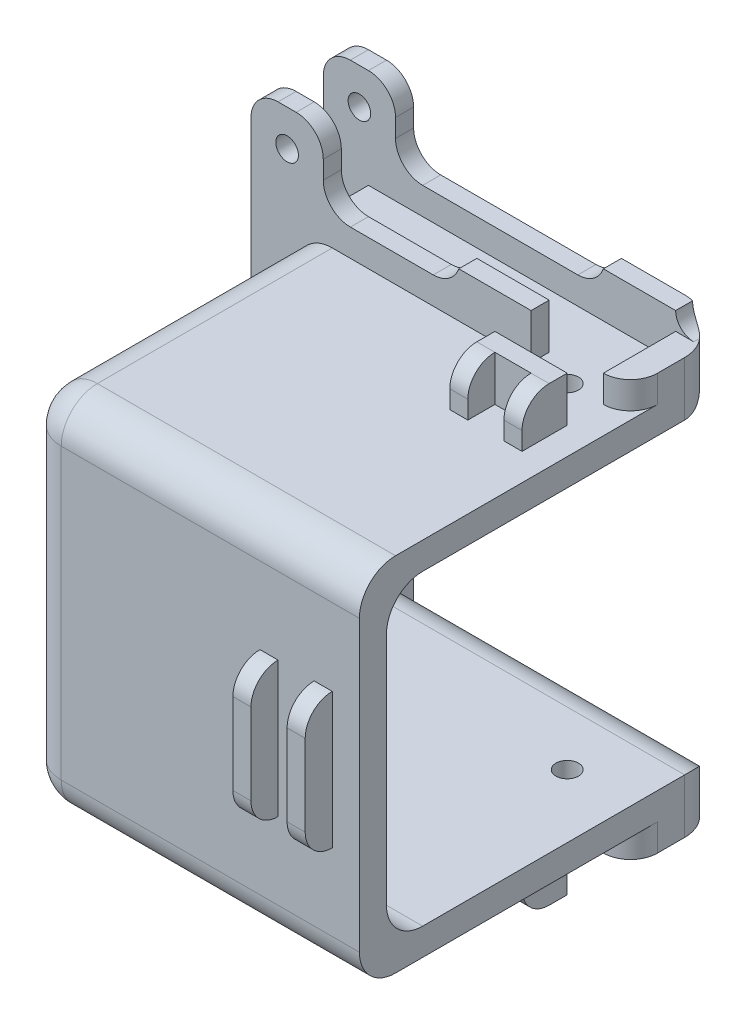
SolidWorks part; units mm, degrees
material "PVC rigido"
ref_plane "Piano frontale" through (0, 0, 0) normal (0, 0, 1) x (1, 0, 0)
ref_plane "Piano superiore" through (0, 0, 0) normal (0, 1, 0) x (1, 0, 0)
ref_plane "Piano destro" through (0, 0, 0) normal (1, 0, 0) x (0, 0, -1)
sketch "Schizzo1" plane through (0, 0, 0) normal (0, 0, 1) x (1, 0, 0)
  line L0 (8, 0) -> (0, 0) construction
  line L1 (0, -23) -> (42, -23)
  line L2 (0, -23) -> (0, 23)
  line L3 (0, 23) -> (42, 23)
  line L4 (42, 23) -> (42, 17)
  line L5 (8, -17) -> (42, -17)
  line L6 (8, -17) -> (8, 17)
  line L7 (8, 17) -> (42, 17)
  line L8 (42, -17) -> (42, -23)
  line L10 (8, 17) -> (8, 20) construction
  line L11 (5, 20) -> (30.5, 20) construction
  dimension "D1" = 6
  dimension "D2" = 42
  dimension "D3" = 3
  dimension "D4" = 8
extrude "Estrusione-Estrusione1" add sketch "Schizzo1" along normal blind 10 contours L2 L3 L4 L7 L6 L5 L8 L1
sketch "Schizzo6" plane through (0, 0, 10) normal (0, 0, 1) x (1, 0, 0)
  line L0 (8, -17) -> (8, 17) construction
  line L1 (0, -23) -> (8, -23)
  line L2 (0, -23) -> (0, -31)
  line L3 (0, -31) -> (8, -31)
  line L4 (8, -23) -> (8, -31)
  line L5 (0, 23) -> (8, 23)
  line L6 (0, 23) -> (0, 31)
  line L7 (0, 31) -> (8, 31)
  line L8 (8, 23) -> (8, 31)
  line L10 (39, -23) -> (31, -23)
  line L11 (39, -23) -> (39, -25)
  line L12 (39, -25) -> (31, -25)
  line L13 (31, -23) -> (31, -25)
  line L14 (39, 23) -> (31, 23)
  line L15 (39, 23) -> (39, 25)
  line L16 (39, 25) -> (31, 25)
  line L17 (31, 23) -> (31, 25)
  line L18 (0, -23) -> (42, -23) construction
  line L19 (0, 23) -> (42, 23) construction
  line L20 (35, -25) -> (35, -23) construction
  line L21 (42, -17) -> (42, -23) construction
  dimension "D1" = 8
  dimension "D2" = 7
  dimension "D3" = 50
extrude "Estrusione-Estrusione4" add sketch "Schizzo6" against normal up to surface (10 mm away) up to face at (23, 0, 0)
sketch "Schizzo2" plane through (42, 0, 0) normal (1, 0, 0) x (0, 0, -1)
  line L0 (-10, -23) -> (0, -23) construction
  line L1 (-8, -23) -> (-8, -41.8171)
  line L2 (-8, -23) -> (-8, -20)
  line L3 (-8, -20) -> (-2, -20)
  line L4 (-2, -22.5) -> (-2, -20)
  line L5 (-5, -20) -> (-5, -17) construction
  line L6 (-10, -17) -> (0, -17) construction
  line L7 (-8, -41.8171) -> (-2, -41.8171)
  line L8 (-2, -41.8171) -> (-2, -22.5)
  dimension "D1" = 3
  dimension "D2" = 6
extrude "Taglio-Estrusione1" cut sketch "Schizzo2" against normal through all
sketch "Schizzo4" plane through (0, -20, 0) normal (0, -1, 0) x (-1, 0, 0)
  line L0 (0, -8) -> (-42, -8) construction
  line L1 (-42, -2) -> (-39, -2)
  line L2 (-42, -2) -> (-42, -8)
  line L3 (-42, -8) -> (-39, -8)
  line L4 (-39, -2) -> (-39, -8)
extrude "Estrusione-Estrusione2" add sketch "Schizzo4" along normal up to surface (3 mm away) up to face at (40.125, -23, 1)
mirror "Specchia1" about plane through (0, 0, 0) normal (0, 1, 0) of "Taglio-Estrusione1"
sketch "Schizzo5" plane through (0, 20, 0) normal (0, 1, 0) x (1, 0, 0)
  line L0 (0, -2) -> (42, -2) construction
  line L1 (42, -2) -> (39, -2)
  line L2 (42, -2) -> (42, -8)
  line L3 (42, -8) -> (39, -8)
  line L4 (39, -2) -> (39, -8)
  line L5 (42, -2) -> (42, -8) construction
  line L6 (0, -8) -> (42, -8) construction
  line L7 (39, -2) -> (39, -8) construction
extrude "Estrusione-Estrusione3" add sketch "Schizzo5" along normal up to surface (3 mm away) up to face at (40.125, 23, 9)
sketch "Schizzo3" plane through (0, -20, 0) normal (0, -1, 0) x (1, 0, 0)
  line L0 (0, 8) -> (39, 8) construction
  line L1 (0, 2) -> (5, 2)
  line L2 (0, 2) -> (0, 8)
  line L3 (0, 8) -> (5, 8)
  line L4 (5, 2) -> (5, 8)
  dimension "D1" = 5
extrude "Taglio-Estrusione2" cut sketch "Schizzo3" against normal through all
hole_wizard "Foro filettato M3x0.5-1" positions "Schizzo8" profile "Schizzo7" tap size "M3x0.5" standard "Ansi Metric" end condition through all
sketch "Schizzo8" plane through (0, 0, 10) normal (0, 0, 1) x (1, 0, 0)
  line L0 (8, -27) -> (4, -27) construction
  line L1 (8, -31) -> (8, -23) construction
  line L2 (4, -27) -> (4, -31) construction
  line L3 (0, -31) -> (8, -31) construction
  line L5 (8, 27) -> (4, 27) construction
  line L6 (8, 23) -> (8, 31) construction
  line L7 (4, 27) -> (4, 31) construction
  line L8 (8, 31) -> (0, 31) construction
  point P0 (4, -27)
  point P2 (4, 27)
sketch "Schizzo7" plane through (4, -27, 10) normal (1, 0, 0) x (0, -1, 0)
  line L0 (0, 0) -> (0, 10)
  line L1 (0, 10) -> (1.25, 10)
  line L2 (1.25, 10) -> (1.25, 0)
  line L5 (1.25, 0) -> (0, 0)
  line L11 (0, -6.35) -> (0, 107.95) construction
  dimension "Thru Tap Drill Dia." = 2.5
  dimension "Thru Tap Drill Depth" = 10
cosmetic thread "Filettatura del foro1" parameters "D2"=3
cosmetic thread "Filettatura del foro2" parameters "D2"=3
sketch "Schizzo9" plane through (0, 0, 10) normal (0, 0, 1) x (1, 0, 0)
  line L0 (42, 23) -> (42, 17) construction
  line L1 (5, -20) -> (42, -20)
  line L2 (5, -20) -> (5, 20)
  line L3 (5, 20) -> (42, 20)
  line L4 (42, -20) -> (42, -17)
  line L5 (42, -17) -> (8, -17)
  line L6 (8, -17) -> (8, 17)
  line L7 (8, -17) -> (8, 17) construction
  line L8 (8, 17) -> (42, 17)
  line L9 (42, 17) -> (42, 20)
  line L10 (42, -17) -> (42, -23) construction
  line L11 (5, 0) -> (8, 0) construction
extrude "Estrusione-Estrusione5" add sketch "Schizzo9" along normal blind 30
sketch "Schizzo10" plane through (8, 0, 0) normal (1, 0, 0) x (0, 0, -1)
  line L0 (-40, 17) -> (0, 17) construction
  line L1 (-40, -17) -> (-37, -17)
  line L2 (-40, -17) -> (-40, 17)
  line L3 (-40, 17) -> (-37, 17)
  line L4 (-37, -17) -> (-37, 17)
  line L5 (-40, -20) -> (-40, -17) construction
extrude "Estrusione-Estrusione6" add sketch "Schizzo10" along normal up to surface (34 mm away) up to face at (42, -19.75, 19.1667)
sketch "Schizzo18" plane through (0, -25, 0) normal (0, -1, 0) x (1, 0, 0)
  line L0 (39, 8) -> (31, 8) construction
  line L1 (31, 8) -> (39, 8)
  line L2 (31, 8) -> (31, 16)
  line L3 (31, 16) -> (39, 16)
  line L4 (39, 8) -> (39, 16)
extrude "Taglio-Estrusione3" cut sketch "Schizzo18" against normal up to surface (5 mm away) up to face at (18.875, -20, 28.75)
sketch "Schizzo24" plane through (0, -20, 0) normal (0, -1, 0) x (1, 0, 0)
  line L0 (31, 8) -> (31, 10) construction
  line L1 (31, 14) -> (39, 14)
  line L2 (31, 14) -> (31, 16)
  line L3 (31, 16) -> (39, 16)
  line L4 (39, 14) -> (39, 16)
  line L5 (39, 2) -> (39, 10) construction
  line L6 (8, 10) -> (31, 10) construction
  dimension "D1" = 4
extrude "Estrusione-Estrusione9" add sketch "Schizzo24" along normal up to surface (5 mm away) up to face at (35, -25, 1)
sketch "Schizzo23" plane through (0, 25, 0) normal (0, 1, 0) x (1, 0, 0)
  line L1 (39, -8) -> (31, -8)
  line L2 (39, -8) -> (39, -16)
  line L3 (39, -16) -> (31, -16)
  line L4 (31, -8) -> (31, -16)
extrude "Taglio-Estrusione4" cut sketch "Schizzo23" against normal up to surface (5 mm away) up to face at (28.125, 20, 28.75)
sketch "Schizzo25" plane through (0, 20, 0) normal (0, 1, 0) x (1, 0, 0)
  line L0 (39, -2) -> (39, -10) construction
  line L1 (39, -14) -> (31, -14)
  line L2 (39, -14) -> (39, -16)
  line L3 (39, -16) -> (31, -16)
  line L4 (31, -14) -> (31, -16)
  line L5 (31, -8) -> (31, -10) construction
  line L6 (31, -14) -> (39, -14) construction
  line L7 (31, -8) -> (31, -10) construction
extrude "Estrusione-Estrusione10" add sketch "Schizzo25" along normal up to surface (5 mm away) up to face at (35, 25, 1)
hole_wizard "Foro filettato M3x0.5-4" positions "Schizzo22" profile "Schizzo21" tap size "M3x0.5" standard "Ansi Metric"
sketch "Schizzo22" plane through (0, -20, 0) normal (0, -1, 0) x (-1, 0, 0)
  line L0 (-35, -10) -> (-35, -40) construction
  line L1 (-5, -40) -> (-42, -40) construction
  line L4 (-31, -10) -> (-35, -10) construction
  line L5 (-35, -10) -> (-39, -10) construction
  point P0 (-35, -10)
sketch "Schizzo21" plane through (35, -20, 10) normal (1, 0, 0) x (0, 0, -1)
  line L0 (0, 0) -> (0, 8.2511)
  line L1 (0, 8.2511) -> (1.25, 7.5)
  line L2 (1.25, 7.5) -> (1.25, 0)
  line L5 (1.25, 0) -> (0, 0)
  line L10 (0, 8.2511) -> (-1.25, 7.5) construction
  line L11 (0, -6.35) -> (0, 107.95) construction
  dimension "Tap Drill Dia." = 2.5
  dimension "Tap Drill Depth" = 7.5
  dimension "Drill Angle" = 118
cosmetic thread "Filettatura del foro5" parameters "D1"=3, "D2"=3
hole_wizard "Foro filettato M3x0.5-5" positions "Schizzo27" profile "Schizzo26" tap size "M3x0.5" standard "Ansi Metric"
sketch "Schizzo27" plane through (0, 20, 0) normal (0, 1, 0) x (1, 0, 0)
  circle A0 centre (35, -10) radius 1.25 construction
  point P0 (35, -10)
sketch "Schizzo26" plane through (35, 20, 10) normal (1, 0, 0) x (0, 0, 1)
  line L0 (0, 0) -> (0, 8.2511)
  line L1 (0, 8.2511) -> (1.25, 7.5)
  line L2 (1.25, 7.5) -> (1.25, 0)
  line L5 (1.25, 0) -> (0, 0)
  line L10 (0, 8.2511) -> (-1.25, 7.5) construction
  line L11 (0, -6.35) -> (0, 107.95) construction
  dimension "Tap Drill Dia." = 2.5
  dimension "Tap Drill Depth" = 7.5
  dimension "Drill Angle" = 118
cosmetic thread "Filettatura del foro6" parameters "D1"=3, "D2"=3
sketch "Schizzo11" plane through (0, 0, 40) normal (0, 0, 1) x (1, 0, 0)
  line L0 (42, 0) -> (39, 0) construction
  line L1 (39, -7.5) -> (37, -7.5)
  line L2 (39, -7.5) -> (39, 7.5)
  line L3 (39, 7.5) -> (37, 7.5)
  line L4 (37, -7.5) -> (37, 7.5)
  line L5 (31, -7.5) -> (33, -7.5)
  line L6 (31, -7.5) -> (31, 7.5)
  line L7 (31, 7.5) -> (33, 7.5)
  line L8 (33, -7.5) -> (33, 7.5)
  line L9 (42, -20) -> (42, 20) construction
  line L10 (39, 0) -> (37, 0) construction
  line L11 (37, 0) -> (33, 0) construction
  line L12 (33, 0) -> (31, 0) construction
  dimension "D1" = 2
  dimension "D2" = 15
  dimension "D3" = 4
  dimension "D4" = 11
extrude "Estrusione-Estrusione7" add sketch "Schizzo11" along normal blind 3
sketch "Schizzo12" plane through (0, 0, 16) normal (0, 0, 1) x (1, 0, 0)
  line L0 (39, -20) -> (42, -20) construction
  line L1 (39, -25) -> (37, -25)
  line L2 (39, -25) -> (39, -20)
  line L3 (39, -20) -> (37, -20)
  line L4 (37, -25) -> (37, -20)
  line L5 (33, -7.5) -> (33, 7.5) construction
  line L6 (31, -25) -> (33, -25)
  line L7 (31, -25) -> (31, -20)
  line L8 (31, -20) -> (33, -20)
  line L9 (33, -25) -> (33, -20)
  line L10 (37, 7.5) -> (37, -7.5) construction
extrude "Estrusione-Estrusione8" add sketch "Schizzo12" along normal blind 3
sketch "Schizzo28" plane through (0, -23, 0) normal (0, -1, 0) x (1, 0, 0)
  line L0 (8, 8) -> (31, 8) construction
  line L1 (31, 10) -> (23, 10)
  line L2 (31, 10) -> (31, 8)
  line L3 (31, 8) -> (23, 8)
  line L4 (23, 10) -> (23, 8)
  line L5 (31, 2) -> (39, 2) construction
extrude "Estrusione-Estrusione11" add sketch "Schizzo28" along normal up to surface (2 mm away) up to face at (35, -25, 1)
sketch "Schizzo29" plane through (0, 23, 0) normal (0, 1, 0) x (1, 0, 0)
  line L0 (8, -10) -> (31, -10) construction
  line L1 (31, -8) -> (23, -8)
  line L2 (31, -8) -> (31, -10)
  line L3 (31, -10) -> (23, -10)
  line L4 (23, -8) -> (23, -10)
  line L5 (39, 0) -> (31, 0) construction
extrude "Estrusione-Estrusione12" add sketch "Schizzo29" along normal up to surface (2 mm away) up to face at (35, 25, 1)
mirror "Specchia2" about plane through (0, 0, 0) normal (0, 1, 0) of "Estrusione-Estrusione8"
fillet "Raccordo1" radius 4 11 edges at (23.5, -20, 40) (23.5, 20, 40) (5, 0, 40) (5, 20, 25) (5, -20, 25) (42, 20, 0) (42, -20, 0) (25, -17, 37) (25, -17, 0) (25, 17, 37) (25, 17, 0)
fillet "Raccordo2" radius 3 26 edges at (32, 25, 19) (38, 25, 19) (38, 7.5, 43) (32, 7.5, 43) (32, -7.5, 43) (38, -7.5, 43) (32, -25, 19) (38, -25, 19) (8, -31, 1) (8, -31, 9) (0, -31, 1) (0, -31, 9) (0, 31, 1) (0, 31, 9) (8, 31, 1) (8, 31, 9) (23, 23, 9) (31, 23, 1) (31, -23, 1) (23, -23, 9)
fillet "Raccordo30" radius 2 2 edges at (39, 23, 1.0635) (39, -23, 1.0635)
